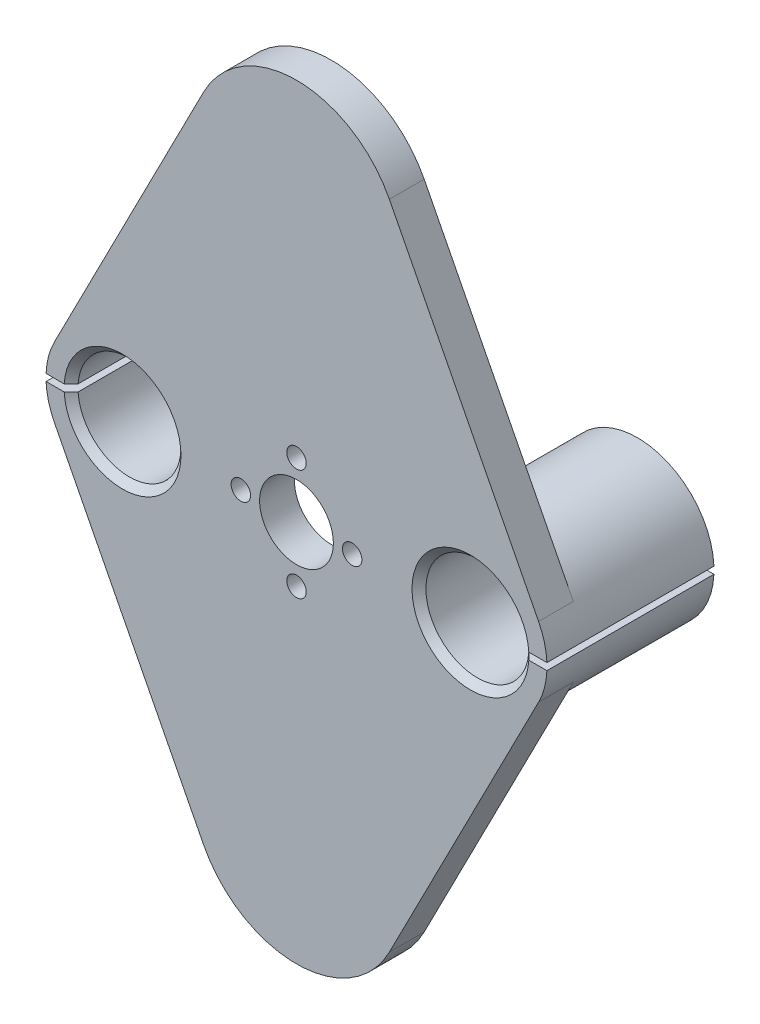
SolidWorks part; units mm, degrees
ref_plane "Płaszczyzna przednia" through (0, 0, 0) normal (0, 0, 1) x (1, 0, 0)
ref_plane "Płaszczyzna górna" through (0, 0, 0) normal (0, 1, 0) x (1, 0, 0)
ref_plane "Płaszczyzna prawa" through (0, 0, 0) normal (1, 0, 0) x (0, 0, -1)
sketch "Sketch1" plane through (0, 0, 0) normal (0, 0, 1) x (1, 0, 0)
  line L0 (0, 110) -> (0, 0) construction
  line L1 (-36, 55) -> (36, 55) construction
  line L2 (-34.7888, 60.018) -> (-13.3483, 101.8427)
  line L3 (-34.7888, 49.982) -> (-13.3483, 8.1573)
  line L4 (34.7888, 49.982) -> (13.3483, 8.1573)
  line L5 (34.7888, 60.018) -> (13.3483, 101.8427)
  arc A0 (13.3483, 101.8427) -> (-13.3483, 101.8427) centre (0, 95) ccw
  arc A1 (13.3483, 8.1573) -> (-13.3483, 8.1573) centre (0, 15) cw
  arc A2 (-34.7888, 60.018) -> (-34.7888, 49.982) centre (-25, 55) ccw
  arc A3 (34.7888, 60.018) -> (34.7888, 49.982) centre (25, 55) cw
  circle A4 centre (0, 55) radius 5.3
  point P3 (0, 55)
  dimension "D4" = 30
  dimension "D5" = 22
  dimension "D6" = 10.6
  dimension "D1" = 110
  dimension "D2" = 72
  dimension "D3" = 72
extrude "Boss-Extrude1" add sketch "Sketch1" along normal blind 5
sketch "Sketch2" plane through (0, 0, 0) normal (0, 0, -1) x (-1, 0, 0)
  circle A0 centre (-25, 55) radius 11
  circle A1 centre (25, 55) radius 11
  arc A4 (-34.7888, 60.018) -> (-34.7888, 49.982) centre (-25, 55) ccw construction
  arc A5 (34.7888, 49.982) -> (34.7888, 60.018) centre (25, 55) ccw construction
  dimension "D1" = 22
  dimension "D2" = 22
extrude "Boss-Extrude2" add sketch "Sketch2" along normal blind 19
sketch "Sketch3" plane through (0, 0, -19) normal (0, 0, -1) x (-1, 0, 0)
  circle A0 centre (-25, 55) radius 7.4
  circle A1 centre (25, 55) radius 7.4
  arc A2 (-34.7888, 49.982) -> (-34.7888, 60.018) centre (-25, 55) ccw construction
  dimension "D1" = 14.8
extrude "Cut-Extrude1" cut sketch "Sketch3" against normal up to next
sketch "Sketch4" plane through (0, 0, 5) normal (0, 0, 1) x (1, 0, 0)
  line L0 (-25, 55) -> (25, 55) construction
  circle A0 centre (-8, 55) radius 1.4
  circle A3 centre (0, 55) radius 5.3 construction
  point P5 (0, 55)
  dimension "3,5" = 2.8
  dimension "D1" = 8
ref_plane "Plane1" through (36, 0, 0) normal (1, 0, 0) x (0, 0, -1)
sketch "Sketch6" plane through (36, 0, 0) normal (1, 0, 0) x (0, 0, -1)
  line L0 (-5, 60.018) -> (-5, 49.982) construction
  line L1 (-5, 55.5) -> (19, 55.5)
  line L2 (-5, 55.5) -> (-5, 54.5)
  line L3 (-5, 54.5) -> (19, 54.5)
  line L4 (19, 55.5) -> (19, 54.5)
  line L5 (7, 54.5) -> (7, 55.5) construction
  line L6 (-5, 55) -> (19, 55) construction
  line L7 (19, 44) -> (19, 66) construction
  point P8 (19, 66)
  point P9 (19, 44)
  point P236 (7, 55)
  dimension "D1" = 22
  dimension "D2" = 1
extrude "Cut-Extrude2" cut sketch "Sketch6" against normal up to next
mirror "Mirror1" about plane through (0, 0, 0) normal (1, 0, 0) of "Cut-Extrude2"
extrude "Cut-Extrude3" cut sketch "Sketch4" against normal up to next
pattern_circular "Szyk kołowy1" count 4 over 360 about axis through (0, 55, 5) along (0, 0, 1) of "Cut-Extrude3"
chamfer "Sfazowanie1" distance 1 angle 45 4 edges at (17.6, 55, -19) (-17.6, 55, -19) (17.6, 55, 5) (-17.6, 55, 5)
